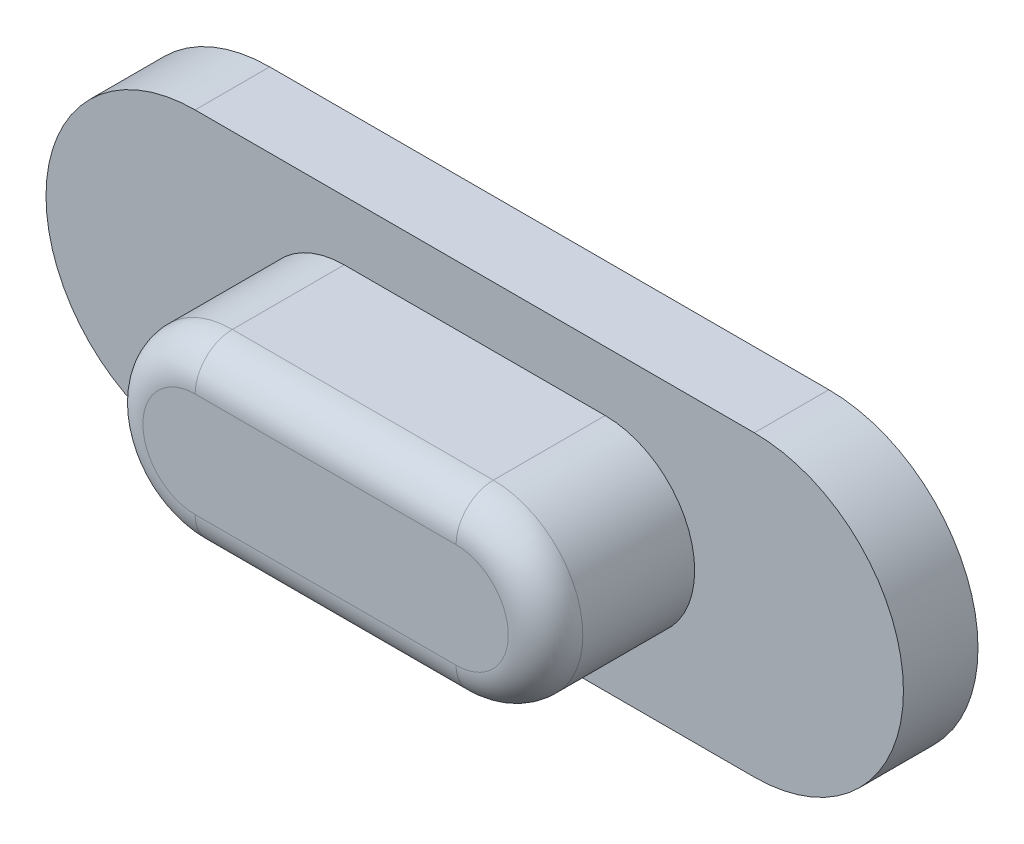
SolidWorks part; units mm, degrees
ref_plane "前视基准面" through (0, 0, 0) normal (0, 0, 1) x (1, 0, 0)
ref_plane "上视基准面" through (0, 0, 0) normal (0, 1, 0) x (1, 0, 0)
ref_plane "右视基准面" through (0, 0, 0) normal (1, 0, 0) x (0, 0, -1)
sketch "草图1" plane through (0, 0, 0) normal (0, 0, 1) x (1, 0, 0)
  line L0 (1.25, 2.5) -> (4.75, 2.5) construction
  line L1 (0, 0) -> (6, 0) construction
  line L2 (0, 0) -> (0, 2.5) construction
  line L3 (0, 2.5) -> (6, 2.5) construction
  line L4 (6, 0) -> (6, 2.5) construction
  line L5 (4.75, 0) -> (1.25, 0) construction
  line L6 (1.25, 2.45) -> (4.75, 2.45)
  line L7 (4.75, 0.05) -> (1.25, 0.05)
  arc A0 (1.25, 2.5) -> (1.25, 0) centre (1.25, 1.25) ccw construction
  arc A1 (4.75, 0) -> (4.75, 2.5) centre (4.75, 1.25) ccw construction
  arc A2 (4.75, 0.05) -> (4.75, 2.45) centre (4.75, 1.25) ccw
  arc A3 (1.25, 2.45) -> (1.25, 0.05) centre (1.25, 1.25) ccw
  dimension "D1" = 6
  dimension "D2" = 2.5
  dimension "D3" = 0.05
extrude "凸台-拉伸1" add sketch "草图1" along normal blind 2
sketch "草图2" plane through (0, 0, 0) normal (0, 0, -1) x (-1, 0, 0)
  line L2 (-4.75, 0.05) -> (-1.25, 0.05)
  line L3 (-4.75, 0.05) -> (-1.25, 0.05)
  line L6 (0.75, 1.25) -> (-6.75, 1.25) construction
  line L7 (0.75, -0.75) -> (-6.75, -0.75)
  line L8 (-1.25, 2.45) -> (-4.75, 2.45)
  line L9 (-1.25, 2.45) -> (-4.75, 2.45)
  line L10 (0.75, 3.25) -> (-6.75, 3.25)
  arc A2 (-1.25, 0.05) -> (-1.25, 2.45) centre (-1.25, 1.25) ccw
  arc A3 (-1.25, 0.05) -> (-1.25, 2.45) centre (-1.25, 1.25) ccw
  arc A6 (0.75, -0.75) -> (0.75, 3.25) centre (0.75, 1.25) ccw
  arc A7 (-6.75, 3.25) -> (-6.75, -0.75) centre (-6.75, 1.25) ccw
  arc A8 (-4.75, 2.45) -> (-4.75, 0.05) centre (-4.75, 1.25) ccw
  arc A9 (-4.75, 2.45) -> (-4.75, 0.05) centre (-4.75, 1.25) ccw
  point P4 (-3, 1.25)
  point P9 (0, 0)
  point P10 (0, 0)
  point P11 (0, 0)
  point P14 (0.219, 1.25)
  point P15 (0, 0)
  point P17 (0, 0)
  point P19 (0, 0)
  point P20 (0, 0)
  arc M17 (-4.75, 2.45) -> (-4.75, 0.05) centre (-4.75, 1.25) ccw
  line M18 (-4.75, 0.05) -> (-1.25, 0.05)
  arc M19 (-1.25, 0.05) -> (-1.25, 2.45) centre (-1.25, 1.25) ccw
  line M20 (-1.25, 2.45) -> (-4.75, 2.45)
  dimension "D2" = 4
  dimension "D3" = 2
  dimension "D4" = 2
  dimension "D1" = 0
extrude "凸台-拉伸2" add sketch "草图2" along normal blind 1 contours L10 | M20 M17 M18 M19 region at (3, 1.25, 0) region at (3, -0.6282, 0)
fillet "圆角1" radius 0.5 4 edges at (0.05, 1.25, 2) (3, 0.05, 2) (5.95, 1.25, 2) (3, 2.45, 2)
